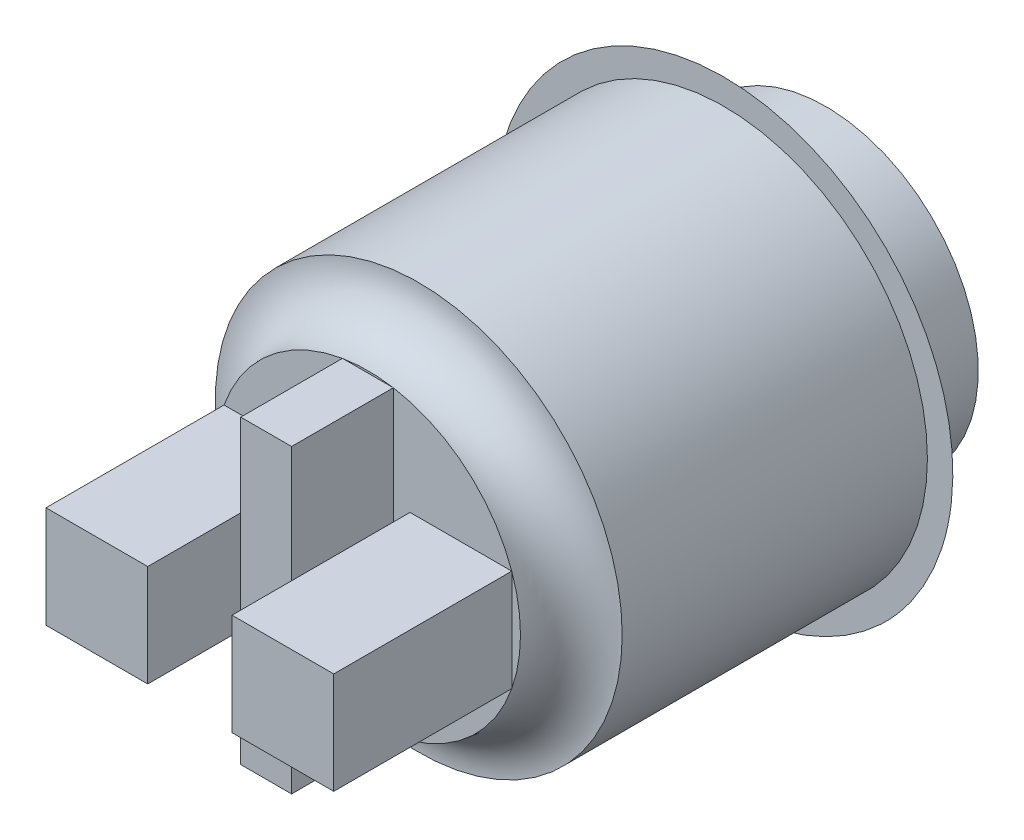
SolidWorks part; units mm, degrees
material "6061 Alloy"
ref_plane "Front Plane" through (0, 0, 0) normal (0, 0, 1) x (1, 0, 0)
ref_plane "Top Plane" through (0, 0, 0) normal (0, 1, 0) x (1, 0, 0)
ref_plane "Right Plane" through (0, 0, 0) normal (1, 0, 0) x (0, 0, -1)
sketch "Sketch1" plane through (0, 0, 0) normal (0, 0, 1) x (1, 0, 0)
  circle A0 centre (0, 0) radius 8
extrude "Boss-Extrude1" add sketch "Sketch1" along normal blind 12
sketch "Sketch2" plane through (0, 0, 0) normal (0, 0, -1) x (-1, 0, 0)
  circle A0 centre (0, 0) radius 9
ref_plane "Plane1" through (0, 0, -2) normal (0, 0, -1) x (-1, 0, 0)
ref_point "Point1"
sketch "Sketch3" plane through (0, 0, -2) normal (0, 0, -1) x (-1, 0, 0)
  circle A0 centre (0, 0) radius 6
loft "Loft1" add profiles "Sketch3", "Sketch2" connector at (-5.9552, 0.7315, -2) connector at (-8.0496, 4.0253, 0)
sketch "Sketch5" plane through (0, 0, -2) normal (0, 0, -1) x (-1, 0, 0)
  circle A0 centre (0, 0) radius 6
extrude "Boss-Extrude2" add sketch "Sketch5" along normal blind 2
sketch "Sketch6" plane through (0, 0, 12) normal (0, 0, 1) x (1, 0, 0)
  circle A0 centre (0, 0) radius 6
extrude "Boss-Extrude3" add sketch "Sketch6" along normal blind 2
fillet "Fillet2" radius 2 1 edges at (6, 0, 12) type face fillet first side face at (6, 0, 14) second side face at (6, 0, 12)
sketch "Sketch7" plane through (0, 0, 14) normal (0, 0, 1) x (1, 0, 0)
  line L0 (0, 0) -> (-6, 0) construction
  line L1 (-5.6569, 2) -> (-5.6569, -2)
  line L2 (-5.6569, 2) -> (-1.6569, 2)
  line L3 (-1.6569, 2) -> (-1.6569, -2)
  line L4 (-1.6569, -2) -> (-5.6569, -2)
  line L5 (0, 0) -> (6, 0) construction
  line L6 (5.6569, 2) -> (5.6569, -2)
  line L7 (5.6569, 2) -> (1.6569, 2)
  line L8 (1.6569, 2) -> (1.6569, -2)
  line L9 (1.6569, -2) -> (5.6569, -2)
  circle A0 centre (0, 0) radius 6 construction
  dimension "D1" = 4
  dimension "D2" = 4
  dimension "D3" = 4
  dimension "D4" = 4
  dimension "D5" = 4
extrude "Boss-Extrude4" add sketch "Sketch7" along normal blind 7
sketch "Sketch8" plane through (0, 0, 14) normal (0, 0, 1) x (1, 0, 0)
  line L0 (0, 6) -> (0, -6) construction
  line L1 (-1, -5.9161) -> (1, -5.9161) construction
  line L2 (1, -5.9161) -> (1, 5.9161)
  line L3 (-1, -5.9161) -> (-1, 5.9161)
  line L4 (-1, 5.9161) -> (1, 5.9161)
  line L5 (-1, -5.9161) -> (1, -5.9161)
  arc A0 (5.6569, 2) -> (-5.6569, 2) centre (0, 0) ccw construction
  arc A1 (-5.6569, -2) -> (5.6569, -2) centre (0, 0) ccw construction
  dimension "D1" = 2
extrude "Boss-Extrude5" add sketch "Sketch8" along normal blind 4
sketch "Sketch10" plane through (0, 0, -4) normal (0, 0, -1) x (-1, 0, 0)
  line L0 (0, 15) -> (0, -15)
  arc A0 (0, 15) -> (0, -15) centre (0, 0) cw
  dimension "D1" = 30
revolve "Revolve1" [suppressed] add sketch "Sketch10" angle 180 about L0
ref_plane "Plane2" through (0, 0, -19) normal (0, 0, -1) x (-1, 0, 0)
sketch "Sketch11" plane through (0, 0, -19) normal (0, 0, -1) x (-1, 0, 0)
  point P0 (0, 0)
ref_plane "Plane3" through (0, 0, -4) normal (0, 0, -1) x (-1, 0, 0)
ref_point "Point2" [suppressed]
